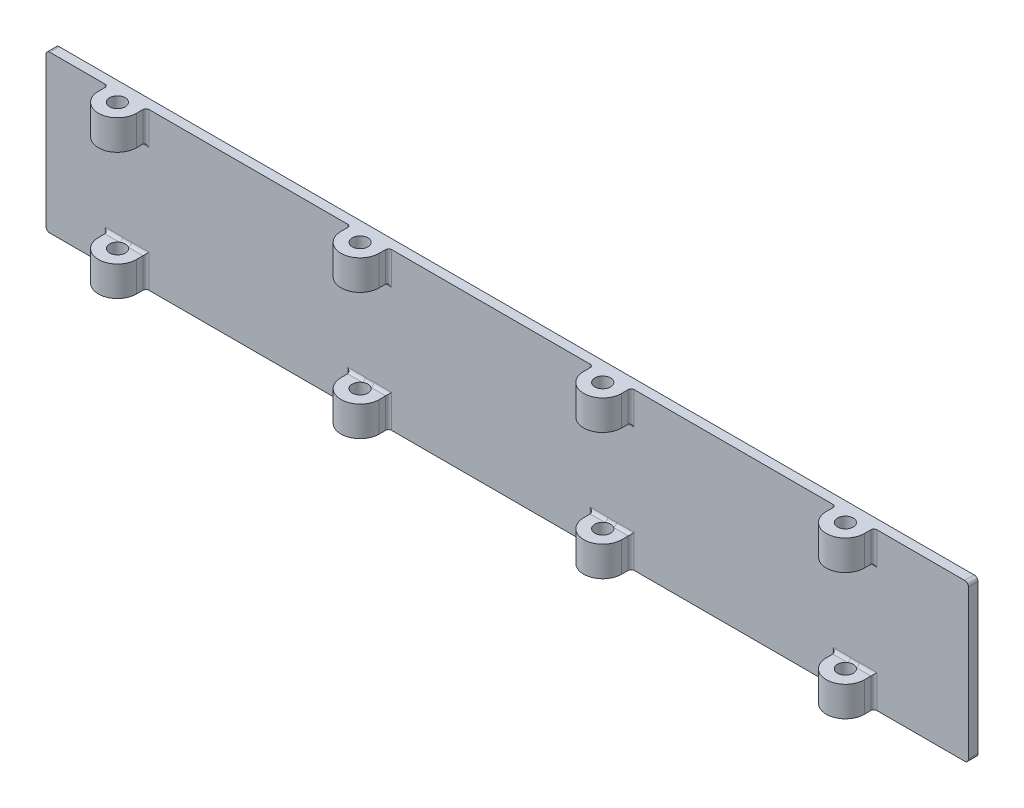
SolidWorks part; units mm, degrees
material "ABS"
ref_plane "X-Y Datum" through (0, 0, 0) normal (0, 0, 1) x (1, 0, 0)
ref_plane "X-Z Datum" through (0, 0, 0) normal (0, 1, 0) x (1, 0, 0)
ref_plane "Y-Z Datum" through (0, 0, 0) normal (1, 0, 0) x (0, 0, -1)
sketch "Sketch1" plane through (0, 0, 0) normal (0, 0, 1) x (1, 0, 0)
  line L1 (0, 0) -> (308.0512, 0)
  line L2 (0, 0) -> (0, 52.3)
  line L3 (0, 52.3) -> (308.0512, 52.3)
  line L4 (308.0512, 0) -> (308.0512, 52.3)
extrude "Boss-Extrude1" add sketch "Sketch1" along normal blind 3.175
fillet "Fillet1" radius 1.27 4 edges at (0, 0, 1.5875) (0, 52.3, 1.5875) (308.0512, 0, 1.5875) (308.0512, 52.3, 1.5875)
sketch "Sketch3" plane through (0, 52.3, 0) normal (0, 1, 0) x (1, 0, 0)
  line L0 (0, 0) -> (19.05, 0) construction
  line L1 (306.7812, 0) -> (1.27, 0) construction
  line L2 (0, -3.175) -> (27.03, -3.175) construction
  line L3 (306.7812, -3.175) -> (1.27, -3.175) construction
  line L4 (20.68, -6.35) -> (20.68, -3.175)
  line L5 (33.38, -6.35) -> (33.38, -3.175)
  line L6 (101.706, -6.35) -> (101.706, -3.175)
  line L7 (114.406, -6.35) -> (114.406, -3.175)
  line L8 (182.732, -6.35) -> (182.732, -3.175)
  line L9 (195.432, -6.35) -> (195.432, -3.175)
  line L10 (263.758, -6.35) -> (263.758, -3.175)
  line L11 (276.458, -6.35) -> (276.458, -3.175)
  line L12 (20.68, -3.175) -> (33.38, -3.175)
  line L13 (101.706, -3.175) -> (114.406, -3.175)
  line L14 (182.732, -3.175) -> (195.432, -3.175)
  line L15 (263.758, -3.175) -> (276.458, -3.175)
  arc A0 (20.68, -6.35) -> (33.38, -6.35) centre (27.03, -6.35) ccw
  arc A1 (101.706, -6.35) -> (114.406, -6.35) centre (108.056, -6.35) ccw
  arc A2 (182.732, -6.35) -> (195.432, -6.35) centre (189.082, -6.35) ccw
  arc A3 (263.758, -6.35) -> (276.458, -6.35) centre (270.108, -6.35) ccw
  dimension "D1" = 4
extrude "Boss-Extrude2" add sketch "Sketch3" against normal blind 10 contours A0 L5 L12 L4 | A1 L7 L13 L6 | A2 L9 L14 L8 | A3 L11 L15 L10
sketch "Sketch4" plane through (0, 52.3, 0) normal (0, 1, 0) x (1, 0, 0)
  circle A0 centre (27.03, -6.35) radius 2.625
  circle A1 centre (108.056, -6.35) radius 2.625
  circle A2 centre (189.082, -6.35) radius 2.625
  circle A3 centre (270.108, -6.35) radius 2.625
extrude "Cut-Extrude1" cut sketch "Sketch4" against normal up to surface (10 mm away) up to face at (108.056, 42.3, 6.35)
ref_plane "Plane1" through (0, 26.15, 0) normal (0, 1, 0) x (1, 0, 0)
mirror "Mirror1" about plane through (0, 26.15, 0) normal (0, 1, 0) of "Cut-Extrude1", "Boss-Extrude2"
fillet "Fillet3" radius 1 24 edges at (20.68, 47.3, 3.175) (27.03, 42.3, 3.175) (33.38, 47.3, 3.175) (33.38, 5, 3.175) (27.03, 10, 3.175) (20.68, 5, 3.175) (101.706, 47.3, 3.175) (108.056, 42.3, 3.175) (114.406, 47.3, 3.175) (114.406, 5, 3.175) (101.706, 5, 3.175) (108.056, 10, 3.175) (182.732, 47.3, 3.175) (189.082, 42.3, 3.175) (195.432, 47.3, 3.175) (195.432, 5, 3.175) (189.082, 10, 3.175) (182.732, 5, 3.175) (263.758, 5, 3.175) (270.108, 10, 3.175) (276.458, 5, 3.175) (276.458, 47.3, 3.175) (270.108, 42.3, 3.175) (263.758, 47.3, 3.175)
